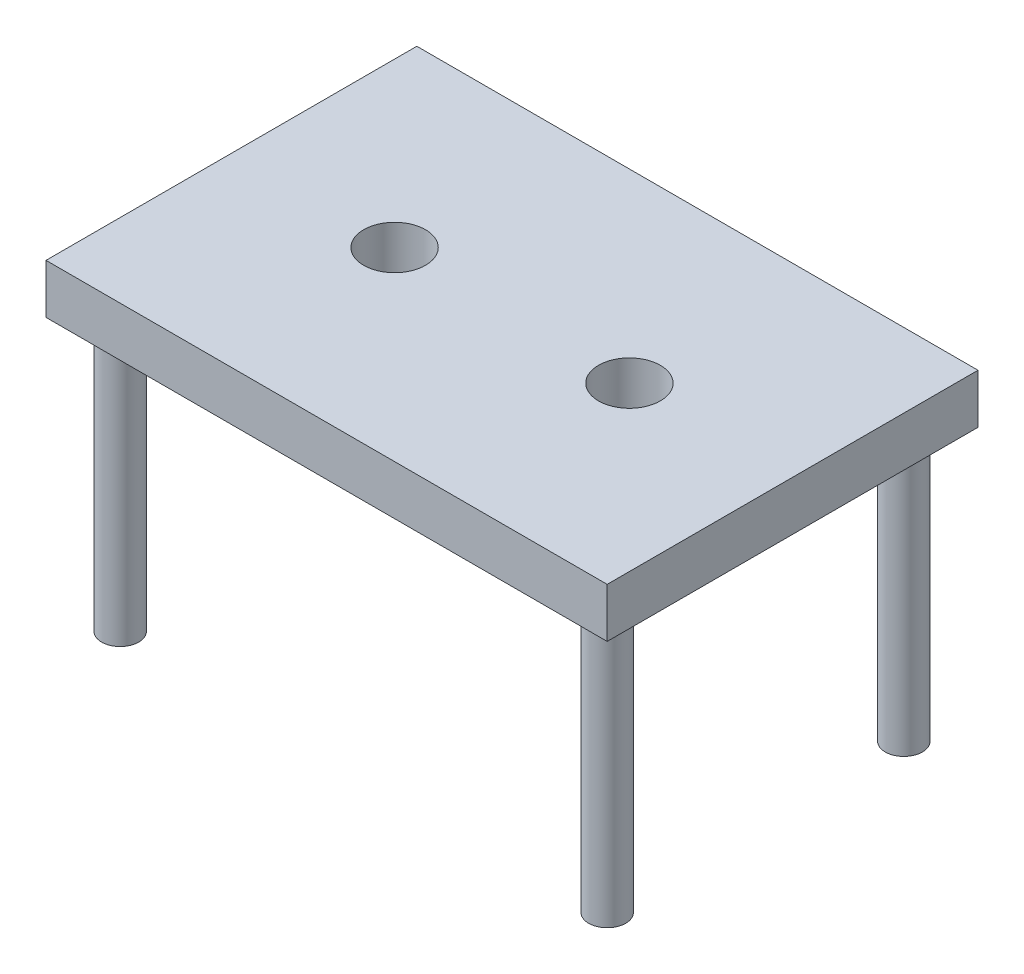
SolidWorks part; units mm, degrees
ref_plane "Front Plane" through (0, 0, 0) normal (0, 0, 1) x (1, 0, 0)
ref_plane "Top Plane" through (0, 0, 0) normal (0, 1, 0) x (1, 0, 0)
ref_plane "Right Plane" through (0, 0, 0) normal (1, 0, 0) x (0, 0, -1)
sketch "Sketch1" plane through (0, 0, 0) normal (0, 1, 0) x (1, 0, 0)
  line L1 (-22.7, -15) -> (22.7, -15)
  line L2 (-22.7, -15) -> (-22.7, 15)
  line L3 (-22.7, 15) -> (22.7, 15)
  line L4 (22.7, -15) -> (22.7, 15)
  line L5 (-22.7, -15) -> (22.7, 15) construction
  line L6 (-22.7, 15) -> (22.7, -15) construction
  point P0 (0, 0)
  dimension "D1" = 45.4
  dimension "D2" = 30
extrude "Boss-Extrude1" add sketch "Sketch1" along normal blind 4
sketch "Sketch2" plane through (0, 4, 0) normal (0, 1, 0) x (1, 0, 0)
  line L0 (-22.7, 15) -> (-22.7, -15) construction
  line L1 (22.7, -15) -> (22.7, 15) construction
  line L2 (22.7, 15) -> (-22.7, 15) construction
  circle A0 centre (-9.5, 0) radius 2.5
  circle A1 centre (9.5, 0) radius 2.5
  dimension "D1" = 5
  dimension "D2" = 5
  dimension "D3" = 13.2
  dimension "D4" = 13.2
  dimension "D5" = 15
  dimension "D6" = 15
extrude "Cut-Extrude1" cut sketch "Sketch2" against normal through all
sketch "Sketch3" plane through (0, 0, 0) normal (0, -1, 0) x (1, 0, 0)
  line L0 (-22.7, -15) -> (-22.7, 15) construction
  line L1 (-22.7, 15) -> (22.7, 15) construction
  line L2 (22.7, 15) -> (22.7, -15) construction
  line L3 (22.7, -15) -> (-22.7, -15) construction
  circle A0 centre (-19.7, 12) radius 1.5
  circle A1 centre (19.7, 12) radius 1.5
  circle A2 centre (-19.7, -12) radius 1.5
  circle A3 centre (19.7, -12) radius 1.5
  dimension "D1" = 3
  dimension "D2" = 3
  dimension "D3" = 3
  dimension "D4" = 3
  dimension "D5" = 3
  dimension "D6" = 3
  dimension "D7" = 3
  dimension "D8" = 3
  dimension "D9" = 3
  dimension "D10" = 3
  dimension "D11" = 3
  dimension "D12" = 3
extrude "Boss-Extrude2" add sketch "Sketch3" along normal blind 22
fillet "Fillet1" radius 1.5 4 edges at (19.7, 0, 10.5) (-19.7, 0, 10.5) (-19.7, 0, -13.5) (19.7, 0, -13.5)
